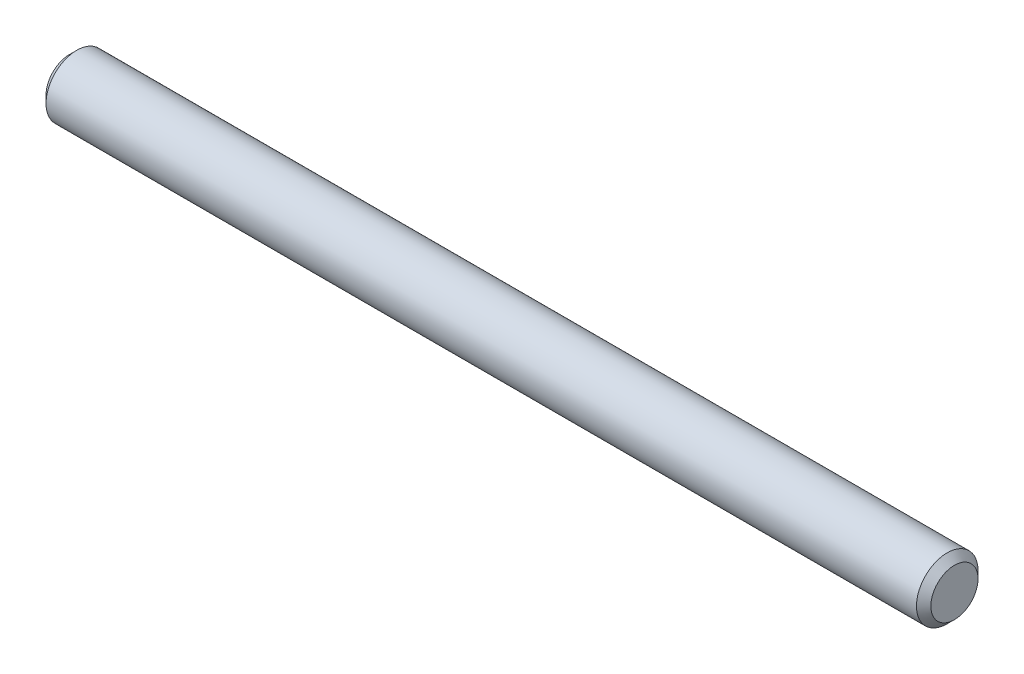
SolidWorks part; units mm, degrees
material "AISI 304"
ref_plane "Front Plane" through (0, 0, 0) normal (0, 0, 1) x (1, 0, 0)
ref_plane "Top Plane" through (0, 0, 0) normal (0, 1, 0) x (1, 0, 0)
ref_plane "Right Plane" through (0, 0, 0) normal (1, 0, 0) x (0, 0, -1)
sketch "Sketch1" plane through (0, 0, 0) normal (0, 0, 1) x (1, 0, 0)
  line L0 (-57.5, 0) -> (57.5, 0) construction
  line L1 (57.5, 4) -> (57.5, -4) construction
  line L2 (-57.5, 4) -> (-57.5, -4) construction
  point P6 (53.125, -4)
  dimension "Thread Diameter" = 8
  dimension "Length" = 115
  dimension "D1" = 4.375
sketch "Sketch2" plane through (0, 0, 0) normal (1, 0, 0) x (0, 0, -1)
  circle A0 centre (0, 0) radius 4
extrude "Boss-Extrude1" add sketch "Sketch2" against normal up to vertex (57.5 mm away) and the other way up to vertex (57.5 mm away) up to point (-57.5, 0, 0) other way up to point (57.5, 0, 0)
sketch "Sketch3" plane through (57.5, 0, 0) normal (1, 0, 0) x (0, 0, -1)
  circle A1 centre (0, 0) radius 4
  circle A2 centre (0, 0) radius 4
  dimension "D1" = 0
curve "Helix/Spiral1" [suppressed] pitch 1.25 height 116.25 turns 93 parameters "Pitch"=1.25
chamfer "Chamfer1" distance 0.9375 angle 45 2 edges at (-57.5, 0, -4) (57.5, 0, -4)
sketch "Sketch4" plane through (0, 0, 0) normal (0, 0, 1) x (1, 0, 0)
  line L0 (57.4219, 4.1353) -> (58.0469, 3.0528) construction
  line L1 (58.0469, 3.0528) -> (58.6719, 4.1353) construction
  line L2 (58.6719, 4.1353) -> (57.4219, 4.1353) construction
  line L3 (58.0469, 4.1353) -> (58.0469, 4) construction
  line L4 (58.0469, 3.0528) -> (58.0469, 3.1881) construction
  line L5 (57.9688, 3.1881) -> (58.125, 3.1881) construction
  line L6 (57.5, 4) -> (58.5938, 4) construction
  line L7 (57.9688, 3.1881) -> (57.4609, 4.0677)
  line L8 (57.9688, 3.1881) -> (58.125, 3.1881)
  line L9 (57.4609, 4.0677) -> (58.6328, 4.0677)
  line L10 (58.6328, 4.0677) -> (58.125, 3.1881)
  point P13 (58.0469, 4.0677)
  dimension "D2" = 0.1562
sweep "Cut-Sweep3" [suppressed] cut profiles "Sketch4" path "Helix/Spiral1"
equation "\"D3@Helix/Spiral1\" = \"Length@Sketch1\"+\"Pitch@Helix/Spiral1\""
equation "\"D1@Chamfer1\" = \"Pitch@Helix/Spiral1\"*.75"
equation "\"D1@Sketch4\" = \"Pitch@Helix/Spiral1\""
equation "\"D2@Sketch4\" = \"D1@Sketch4\"/8"
equation "\"D1@Sketch1\" = \"Pitch@Helix/Spiral1\"*3.50"
